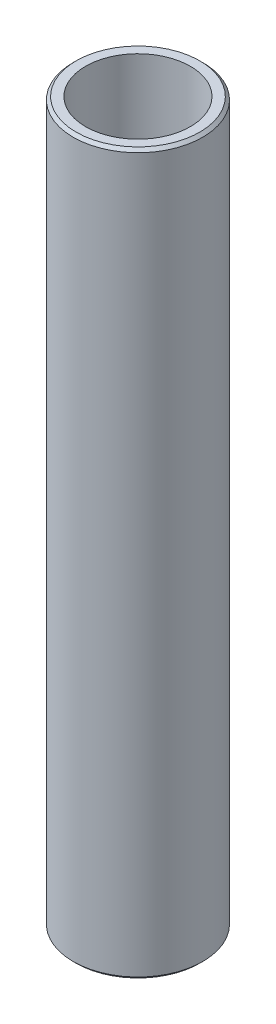
SolidWorks part; units mm, degrees
ref_plane "Front Plane" through (0, 0, 0) normal (0, 0, 1) x (1, 0, 0)
ref_plane "Top Plane" through (0, 0, 0) normal (0, 1, 0) x (1, 0, 0)
ref_plane "Right Plane" through (0, 0, 0) normal (1, 0, 0) x (0, 0, -1)
sketch "Sketch1" plane through (0, 0, 0) normal (0, 1, 0) x (1, 0, 0)
  circle A0 centre (0, 0) radius 32.5
  dimension "SHAFT_OD" = 65
extrude "Boss-Extrude1" add sketch "Sketch1" along normal blind 361.1804
sketch "Sketch2" plane through (0, 0, 0) normal (0, 1, 0) x (1, 0, 0)
  circle A0 centre (0, 0) radius 26.2833
  dimension "BORE_D" = 52.5667
extrude "Cut-Extrude1" cut sketch "Sketch2" along normal through all
chamfer "Chamfer1" distance 1.4848 angle 45 2 edges at (0, 361.1804, 32.5) (0, 0, 32.5)
